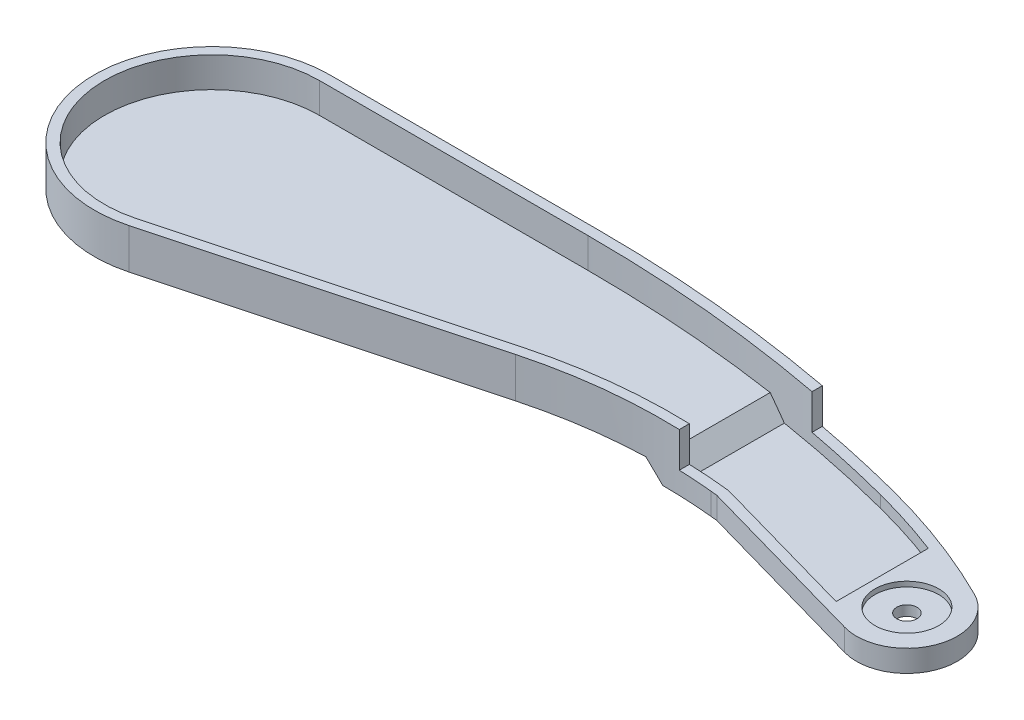
SolidWorks part; units mm, degrees
ref_plane "前视基准面" through (0, 0, 0) normal (0, 0, 1) x (1, 0, 0)
ref_plane "上视基准面" through (0, 0, 0) normal (0, 1, 0) x (1, 0, 0)
ref_plane "右视基准面" through (0, 0, 0) normal (1, 0, 0) x (0, 0, -1)
other "Configuration Table"
sketch "草图1" plane through (0, 0, 0) normal (0, 1, 0) x (1, 0, 0)
  line L0 (0, 35) -> (80, 35)
  line L1 (0, 35) -> (0, 0) construction
  line L2 (0, 0) -> (9.0587, -33.8074) construction
  line L3 (9.0587, -33.8074) -> (99.8557, -9.4784)
  line L4 (208.8416, -20.3229) -> (155.7525, -5.3288)
  line L5 (212.9186, -5.8876) -> (212.9186, -20.8876) construction
  line L6 (155.7525, -5.3288) -> (153.7626, -5.1276)
  line L7 (219.6127, 7.5359) -> (212.9186, -5.8876) construction
  circle A0 centre (0, 0) radius 35
  circle A1 centre (212.9186, -5.8876) radius 15
  circle A2 centre (212.9186, -5.8876) radius 3
  arc A3 (99.8557, -9.4784) -> (153.7626, -5.1276) centre (138.6786, -154.3673) cw
  arc A4 (80, 35) -> (180.7174, 22.1124) centre (80, -365) cw
  arc A5 (180.7174, 22.1124) -> (219.6127, 7.5359) centre (130.3587, -171.4438) cw
  dimension "D1" = 70
  dimension "D2" = 30
  dimension "D4" = 6
  dimension "D8" = 150
  dimension "D10" = 400
  dimension "D11" = 200
  dimension "D3" = 213
  dimension "D5" = 165
  dimension "D6" = 94
  dimension "D7" = 170
  dimension "D9" = 80
  dimension "D12" = 28
  dimension "D13" = 2
extrude "凸台-拉伸1" add sketch "草图1" along normal blind 3 contours A0 | A5 A4 L0 A0 L3 A3 L6 L4 A1 | A1 A2 region at (104.517, 0, -9.1148) region at (0, 0, 0) region at (225.3134, 0, -1.7819)
sketch "草图2" plane through (0, 3, 0) normal (0, 1, 0) x (1, 0, 0)
  line L12 (8.2822, -30.9096) -> (99.0792, -6.5806)
  line L13 (154.0643, -2.1429) -> (156.3153, -2.3704)
  line L14 (156.3153, -2.3704) -> (209.657, -17.4358)
  line L15 (80, 32) -> (0, 32)
  line L16 (8.2822, -30.9096) -> (99.0792, -6.5806)
  line L17 (154.0643, -2.1429) -> (156.3153, -2.3704)
  line L18 (156.3153, -2.3704) -> (209.657, -17.4358)
  line L19 (80, 32) -> (0, 32)
  line L20 (9.0587, -33.8074) -> (99.8557, -9.4784)
  line L21 (153.7626, -5.1276) -> (155.7525, -5.3288)
  line L22 (155.7525, -5.3288) -> (208.8416, -20.3229)
  line L23 (80, 35) -> (0, 35)
  line L24 (9.0587, -33.8074) -> (99.8557, -9.4784)
  line L25 (153.7626, -5.1276) -> (155.7525, -5.3288)
  line L26 (155.7525, -5.3288) -> (208.8416, -20.3229)
  line L27 (80, 35) -> (0, 35)
  circle A0 centre (0, 0) radius 30
  circle A6 centre (0, 0) radius 32
  arc A7 (0, 35) -> (9.0587, -33.8074) centre (0, 0) ccw construction
  arc A18 (0, 32) -> (8.2822, -30.9096) centre (0, 0) ccw
  arc A19 (154.0643, -2.1429) -> (99.0792, -6.5806) centre (138.6786, -154.3673) ccw
  arc A20 (209.657, -17.4358) -> (218.2739, 4.8512) centre (212.9186, -5.8876) ccw
  arc A21 (218.2739, 4.8512) -> (179.962, 19.2091) centre (130.3587, -171.4438) ccw
  arc A22 (179.962, 19.2091) -> (80, 32) centre (80, -365) ccw
  arc A23 (0, 32) -> (8.2822, -30.9096) centre (0, 0) ccw
  arc A24 (154.0643, -2.1429) -> (99.0792, -6.5806) centre (138.6786, -154.3673) ccw
  arc A25 (209.657, -17.4358) -> (218.2739, 4.8512) centre (212.9186, -5.8876) ccw
  arc A26 (218.2739, 4.8512) -> (179.962, 19.2091) centre (130.3587, -171.4438) ccw
  arc A27 (179.962, 19.2091) -> (80, 32) centre (80, -365) ccw
  arc A28 (0, 35) -> (9.0587, -33.8074) centre (0, 0) ccw
  arc A29 (153.7626, -5.1276) -> (99.8557, -9.4784) centre (138.6786, -154.3673) ccw
  arc A30 (208.8416, -20.3229) -> (219.6127, 7.5359) centre (212.9186, -5.8876) ccw
  arc A31 (219.6127, 7.5359) -> (180.7174, 22.1124) centre (130.3587, -171.4438) ccw
  arc A32 (180.7174, 22.1124) -> (80, 35) centre (80, -365) ccw
  arc A33 (0, 35) -> (9.0587, -33.8074) centre (0, 0) ccw
  arc A34 (153.7626, -5.1276) -> (99.8557, -9.4784) centre (138.6786, -154.3673) ccw
  arc A35 (208.8416, -20.3229) -> (219.6127, 7.5359) centre (212.9186, -5.8876) ccw
  arc A36 (219.6127, 7.5359) -> (180.7174, 22.1124) centre (130.3587, -171.4438) ccw
  arc A37 (180.7174, 22.1124) -> (80, 35) centre (80, -365) ccw
  arc M1 (0, 35) -> (9.0587, -33.8074) centre (0, 0) ccw
  line M2 (9.0587, -33.8074) -> (99.8557, -9.4784)
  arc M3 (99.8557, -9.4784) -> (153.7626, -5.1276) centre (138.6786, -154.3673) cw
  line M4 (153.7626, -5.1276) -> (155.7525, -5.3288)
  line M5 (155.7525, -5.3288) -> (208.8416, -20.3229)
  arc M6 (208.8416, -20.3229) -> (219.6127, 7.5359) centre (212.9186, -5.8876) ccw
  arc M7 (219.6127, 7.5359) -> (180.7174, 22.1124) centre (130.3587, -171.4438) ccw
  arc M8 (180.7174, 22.1124) -> (80, 35) centre (80, -365) ccw
  line M9 (80, 35) -> (0, 35)
  dimension "D1" = 60
  dimension "D2" = 3
  dimension "D3" = 3
  dimension "D4" = 0
extrude "凸台-拉伸2" add sketch "草图2" along normal blind 9 contours A27 A26 A25 L18 L17 A24 L16 A6 L19 M9 M1 M2 M3 M4 M5 M6 M7 M8 region at (-32.0031, 3, 4.2133)
sketch "草图3" plane through (0, 0, 0) normal (0, -1, 0) x (1, 0, 0)
  line L0 (208.8416, 20.3229) -> (155.7525, 5.3288) construction
  line L1 (155.7525, 5.3288) -> (153.7626, 5.1276) construction
  line L2 (9.0587, 33.8074) -> (99.8557, 9.4784) construction
  line L3 (0, -35) -> (80, -35) construction
  line L4 (208.8416, 20.3229) -> (155.7525, 5.3288)
  line L5 (155.7525, 5.3288) -> (153.7626, 5.1276)
  line L6 (9.0587, 33.8074) -> (99.8557, 9.4784)
  line L7 (0, -35) -> (80, -35)
  line L8 (138.6786, 4.3673) -> (138.6786, -30.6726)
  arc A0 (99.8557, 9.4784) -> (153.7626, 5.1276) centre (138.6786, 154.3673) ccw construction
  circle A1 centre (212.9186, 5.8876) radius 3
  circle A2 centre (212.9186, 5.8876) radius 3
  circle A3 centre (212.9186, 5.8876) radius 15
  circle A4 centre (212.9186, 5.8876) radius 15
  circle A5 centre (0, 0) radius 35
  circle A6 centre (0, 0) radius 35
  arc A7 (80, -35) -> (180.7174, -22.1124) centre (80, 365) ccw construction
  arc A8 (180.7174, -22.1124) -> (219.6127, -7.5359) centre (130.3587, 171.4438) ccw construction
  arc A9 (99.8557, 9.4784) -> (153.7626, 5.1276) centre (138.6786, 154.3673) ccw
  arc A10 (80, -35) -> (180.7174, -22.1124) centre (80, 365) ccw
  arc A11 (180.7174, -22.1124) -> (219.6127, -7.5359) centre (130.3587, 171.4438) ccw
  arc M6 (80, -35) -> (180.7174, -22.1124) centre (80, 365) ccw
  arc M7 (180.7174, -22.1124) -> (219.6127, -7.5359) centre (130.3587, 171.4438) ccw
  arc M8 (219.6127, -7.5359) -> (208.8416, 20.3229) centre (212.9186, 5.8876) ccw
  line M9 (208.8416, 20.3229) -> (155.7525, 5.3288)
  line M10 (155.7525, 5.3288) -> (153.7626, 5.1276)
  arc M11 (153.7626, 5.1276) -> (99.8557, 9.4784) centre (138.6786, 154.3673) cw
  circle M13 centre (212.9186, 5.8876) radius 3
  dimension "D1" = 0
  dimension "D2" = 0
  dimension "D3" = 0
extrude "凸台-拉伸3" add sketch "草图3" along normal blind 5 contours A4 L8 M9 M10 M11 M6 M7 | A4 M8 M13 region at (170.7255, 0, -7.4708) region at (221.7137, 0, 17.5108)
chamfer "倒角2" distance 5 angle 45 1 edges at (138.6786, 0, -13.1527)
sketch "草图5" plane through (0, 3, 0) normal (0, 1, 0) x (1, 0, 0)
  line L0 (0, 35) -> (80, 35) construction
  line L1 (208.8416, -20.3229) -> (155.7525, -5.3288) construction
  line L2 (155.7525, -5.3288) -> (153.7626, -5.1276) construction
  line L3 (9.0587, -33.8074) -> (99.8557, -9.4784) construction
  line L4 (138.6786, -4.3673) -> (138.6786, 30.6726) construction
  line L5 (0, 35) -> (80, 35)
  line L6 (208.8416, -20.3229) -> (155.7525, -5.3288)
  line L7 (155.7525, -5.3288) -> (153.7626, -5.1276)
  line L8 (9.0587, -33.8074) -> (99.8557, -9.4784)
  line L9 (138.6786, -4.3673) -> (138.6786, 30.6726)
  line L14 (80, 32) -> (0, 32)
  line L15 (8.2822, -30.9096) -> (99.0792, -6.5806)
  line L16 (154.0643, -2.1429) -> (156.3153, -2.3704)
  line L17 (156.3153, -2.3704) -> (209.657, -17.4358)
  line L18 (80, 32) -> (0, 32)
  line L19 (8.2822, -30.9096) -> (99.0792, -6.5806)
  line L20 (154.0643, -2.1429) -> (156.3153, -2.3704)
  line L21 (156.3153, -2.3704) -> (209.657, -17.4358)
  arc A0 (180.7174, 22.1124) -> (80, 35) centre (80, -365) ccw construction
  circle A1 centre (0, 0) radius 35
  circle A2 centre (0, 0) radius 35
  circle A3 centre (212.9186, -5.8876) radius 15
  circle A4 centre (212.9186, -5.8876) radius 15
  circle A5 centre (212.9186, -5.8876) radius 3
  circle A6 centre (212.9186, -5.8876) radius 3
  arc A7 (219.6127, 7.5359) -> (180.7174, 22.1124) centre (130.3587, -171.4438) ccw construction
  arc A8 (153.7626, -5.1276) -> (99.8557, -9.4784) centre (138.6786, -154.3673) ccw construction
  arc A9 (180.7174, 22.1124) -> (80, 35) centre (80, -365) ccw
  arc A10 (219.6127, 7.5359) -> (180.7174, 22.1124) centre (130.3587, -171.4438) ccw
  arc A11 (153.7626, -5.1276) -> (99.8557, -9.4784) centre (138.6786, -154.3673) ccw
  arc A17 (179.962, 19.2091) -> (80, 32) centre (80, -365) ccw
  arc A18 (0, 32) -> (8.2822, -30.9096) centre (0, 0) ccw
  arc A19 (154.0643, -2.1429) -> (99.0792, -6.5806) centre (138.6786, -154.3673) ccw
  arc A20 (209.657, -17.4358) -> (218.2739, 4.8512) centre (212.9186, -5.8876) ccw
  arc A21 (218.2739, 4.8512) -> (179.962, 19.2091) centre (130.3587, -171.4438) ccw
  arc A22 (179.962, 19.2091) -> (80, 32) centre (80, -365) ccw
  arc A23 (0, 32) -> (8.2822, -30.9096) centre (0, 0) ccw
  arc A24 (154.0643, -2.1429) -> (99.0792, -6.5806) centre (138.6786, -154.3673) ccw
  arc A25 (209.657, -17.4358) -> (218.2739, 4.8512) centre (212.9186, -5.8876) ccw
  arc A26 (218.2739, 4.8512) -> (179.962, 19.2091) centre (130.3587, -171.4438) ccw
  point P23 (138.6786, 27.6396)
  point P28 (138.6786, -1.3673)
  arc M13 (179.962, 19.2091) -> (80, 32) centre (80, -365) ccw
  arc M17 (99.0792, -6.5806) -> (154.0643, -2.1429) centre (138.6786, -154.3673) cw
  line M18 (154.0643, -2.1429) -> (156.3153, -2.3704)
  line M19 (156.3153, -2.3704) -> (209.657, -17.4358)
  arc M20 (209.657, -17.4358) -> (218.2739, 4.8512) centre (212.9186, -5.8876) ccw
  arc M21 (218.2739, 4.8512) -> (179.962, 19.2091) centre (130.3587, -171.4438) ccw
  circle M22 centre (212.9186, -5.8876) radius 3
  dimension "D1" = 0
  dimension "D2" = 0
  dimension "D3" = 0
  dimension "D4" = 0
extrude "切除-拉伸1" cut sketch "草图5" against normal blind 5 contours A4 L9 M21 M13 M17 M18 M19 | A4 L21 M21 M20 M22 region at (169.892, 3, -7.5421) region at (213.9325, 3, -6.5309)
chamfer "倒角3" distance 5 angle 45 1 edges at (138.6786, -2, -13.1361)
sketch "草图6" plane through (0, 12, 0) normal (0, 1, 0) x (1, 0, 0)
  line L0 (153.6786, 28.1558) -> (153.6786, 25.1032)
  line L1 (143.6786, -1.449) -> (143.6786, -4.4506)
  line L2 (143.6786, 26.8597) -> (143.6786, -1.449) construction
  line L4 (156.3153, -2.3704) -> (209.657, -17.4358)
  line L5 (154.0643, -2.1429) -> (156.3153, -2.3704)
  line L6 (8.2822, -30.9096) -> (99.0792, -6.5806)
  line L7 (80, 32) -> (0, 32)
  line L8 (156.3153, -2.3704) -> (209.657, -17.4358)
  line L9 (154.0643, -2.1429) -> (156.3153, -2.3704)
  line L10 (8.2822, -30.9096) -> (99.0792, -6.5806)
  line L11 (80, 32) -> (0, 32)
  line L12 (80, 35) -> (0, 35)
  line L13 (9.0587, -33.8074) -> (99.8557, -9.4784)
  line L14 (153.7626, -5.1276) -> (155.7525, -5.3288)
  line L15 (155.7525, -5.3288) -> (208.8416, -20.3229)
  line L16 (80, 35) -> (0, 35)
  line L17 (9.0587, -33.8074) -> (99.8557, -9.4784)
  line L18 (153.7626, -5.1276) -> (155.7525, -5.3288)
  line L19 (155.7525, -5.3288) -> (208.8416, -20.3229)
  arc A0 (153.7626, -5.1276) -> (99.8557, -9.4784) centre (138.6786, -154.3673) ccw construction
  arc A5 (179.962, 19.2091) -> (80, 32) centre (80, -365) ccw
  arc A6 (218.2739, 4.8512) -> (179.962, 19.2091) centre (130.3587, -171.4438) ccw
  arc A7 (209.657, -17.4358) -> (218.2739, 4.8512) centre (212.9186, -5.8876) ccw
  arc A8 (154.0643, -2.1429) -> (99.0792, -6.5806) centre (138.6786, -154.3673) ccw
  arc A9 (0, 32) -> (8.2822, -30.9096) centre (0, 0) ccw
  arc A10 (179.962, 19.2091) -> (80, 32) centre (80, -365) ccw
  arc A11 (218.2739, 4.8512) -> (179.962, 19.2091) centre (130.3587, -171.4438) ccw
  arc A12 (209.657, -17.4358) -> (218.2739, 4.8512) centre (212.9186, -5.8876) ccw
  arc A13 (154.0643, -2.1429) -> (99.0792, -6.5806) centre (138.6786, -154.3673) ccw
  arc A14 (0, 32) -> (8.2822, -30.9096) centre (0, 0) ccw
  arc A15 (0, 35) -> (9.0587, -33.8074) centre (0, 0) ccw
  arc A16 (153.7626, -5.1276) -> (99.8557, -9.4784) centre (138.6786, -154.3673) ccw
  arc A17 (208.8416, -20.3229) -> (219.6127, 7.5359) centre (212.9186, -5.8876) ccw
  arc A18 (219.6127, 7.5359) -> (180.7174, 22.1124) centre (130.3587, -171.4438) ccw
  arc A19 (180.7174, 22.1124) -> (80, 35) centre (80, -365) ccw
  arc A20 (0, 35) -> (9.0587, -33.8074) centre (0, 0) ccw
  arc A21 (153.7626, -5.1276) -> (99.8557, -9.4784) centre (138.6786, -154.3673) ccw
  arc A22 (208.8416, -20.3229) -> (219.6127, 7.5359) centre (212.9186, -5.8876) ccw
  arc A23 (219.6127, 7.5359) -> (180.7174, 22.1124) centre (130.3587, -171.4438) ccw
  arc A24 (180.7174, 22.1124) -> (80, 35) centre (80, -365) ccw
  arc M20 (179.962, 19.2091) -> (218.2739, 4.8512) centre (130.3587, -171.4438) cw
  arc M21 (218.2739, 4.8512) -> (209.657, -17.4358) centre (212.9186, -5.8876) cw
  line M22 (209.657, -17.4358) -> (156.3153, -2.3704)
  line M23 (156.3153, -2.3704) -> (154.0643, -2.1429)
  arc M24 (154.0643, -2.1429) -> (99.0792, -6.5806) centre (138.6786, -154.3673) ccw
  arc M31 (99.8557, -9.4784) -> (153.7626, -5.1276) centre (138.6786, -154.3673) cw
  line M32 (153.7626, -5.1276) -> (155.7525, -5.3288)
  line M33 (155.7525, -5.3288) -> (208.8416, -20.3229)
  arc M34 (208.8416, -20.3229) -> (219.6127, 7.5359) centre (212.9186, -5.8876) ccw
  arc M35 (219.6127, 7.5359) -> (180.7174, 22.1124) centre (130.3587, -171.4438) ccw
  dimension "D3" = 10
  dimension "D1" = 0
  dimension "D2" = 0
extrude "切除-拉伸2" cut sketch "草图6" against normal blind 10.5 contours L1 M24 M31 M32 M33 M34 M35 M20 M21 M22 M23 region at (167.0377, 12, -24.417)
sketch "草图7" plane through (0, -2, 0) normal (0, 1, 0) x (1, 0, 0)
  line L0 (200.9186, 12.4863) -> (200.9186, -14.9678)
  line L3 (143.6786, 26.8597) -> (143.6786, -1.449)
  line L4 (154.0643, -2.1429) -> (156.3153, -2.3704)
  line L5 (156.3153, -2.3704) -> (209.657, -17.4358)
  line L6 (143.6786, 26.8597) -> (143.6786, -1.449)
  line L7 (154.0643, -2.1429) -> (156.3153, -2.3704)
  line L8 (156.3153, -2.3704) -> (209.657, -17.4358)
  circle A0 centre (212.9186, -5.8876) radius 3
  circle A1 centre (212.9186, -5.8876) radius 12
  arc A4 (179.962, 19.2091) -> (143.6786, 26.8597) centre (80, -365) ccw
  arc A5 (154.0643, -2.1429) -> (143.6786, -1.449) centre (138.6786, -154.3673) ccw
  arc A6 (209.657, -17.4358) -> (218.2739, 4.8512) centre (212.9186, -5.8876) ccw
  arc A7 (218.2739, 4.8512) -> (179.962, 19.2091) centre (130.3587, -171.4438) ccw
  arc A8 (179.962, 19.2091) -> (143.6786, 26.8597) centre (80, -365) ccw
  arc A9 (154.0643, -2.1429) -> (143.6786, -1.449) centre (138.6786, -154.3673) ccw
  arc A10 (209.657, -17.4358) -> (218.2739, 4.8512) centre (212.9186, -5.8876) ccw
  arc A11 (218.2739, 4.8512) -> (179.962, 19.2091) centre (130.3587, -171.4438) ccw
  circle A12 centre (212.9186, -5.8876) radius 3 construction
  line M14 (156.3153, -2.3704) -> (209.657, -17.4358)
  arc M15 (209.657, -17.4358) -> (218.2739, 4.8512) centre (212.9186, -5.8876) ccw
  arc M16 (218.2739, 4.8512) -> (179.962, 19.2091) centre (130.3587, -171.4438) ccw
  circle M17 centre (212.9186, -5.8876) radius 3
  dimension "D1" = 0
extrude "凸台-拉伸5" add sketch "草图7" along normal up to surface (3.5 mm away) contours A1 L0 M16 | A1 M15 M17 | A1 L0 M14 region at (205.1077, -2, -6.3964) region at (202.8007, -2, 13.5437) region at (206.783, -2, -4.0283) up to face at (175.3835, 1.5, -3.011)
sketch "草图8" plane through (0, 1.5, 0) normal (0, 1, 0) x (1, 0, 0)
  circle A0 centre (212.9186, -5.8876) radius 3 construction
  circle A1 centre (212.9186, -5.8876) radius 3
  circle A2 centre (212.9186, -5.8876) radius 9.5
  dimension "D1" = 19
extrude "切除-拉伸3" cut sketch "草图8" against normal blind 1.5
sketch "草图9" plane through (0, -5, 0) normal (0, -1, 0) x (1, 0, 0)
  circle A0 centre (212.9186, 5.8876) radius 7
  dimension "D1" = 14
extrude "切除-拉伸4" cut sketch "草图9" against normal blind 2
